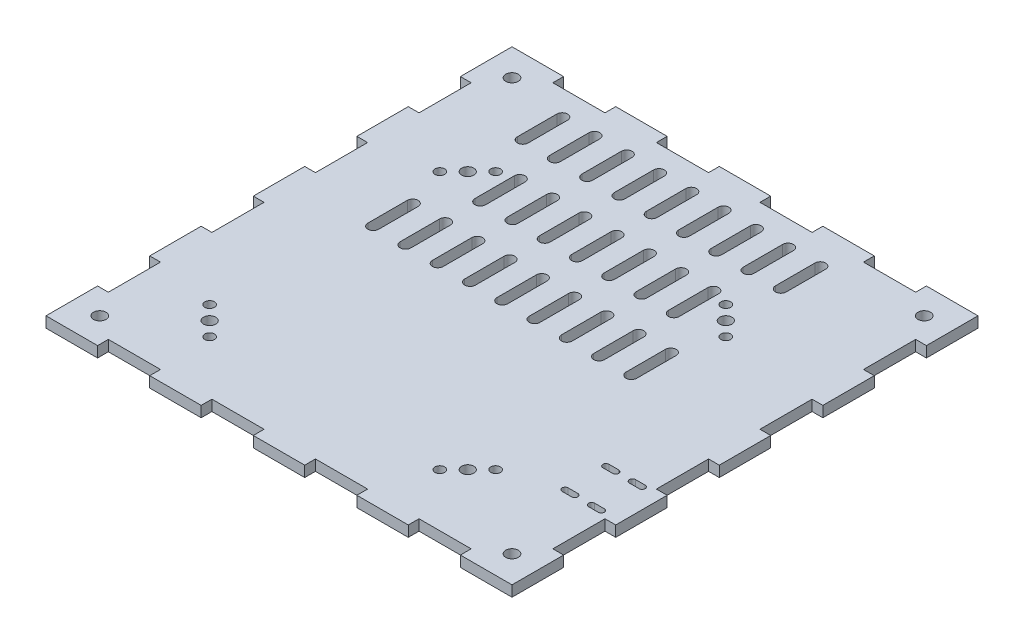
SolidWorks part; units mm, degrees
material "Acrylic (Medium-high impact)"
ref_plane "Front Plane" through (0, 0, 0) normal (0, 0, 1) x (1, 0, 0)
ref_plane "Top Plane" through (0, 0, 0) normal (0, 1, 0) x (1, 0, 0)
ref_plane "Right Plane" through (0, 0, 0) normal (1, 0, 0) x (0, 0, -1)
sketch "Board refrence" plane through (0, 0, 0) normal (0, 1, 0) x (1, 0, 0)
  line L0 (42.5, -17.26) -> (47.5, -17.26)
  line L1 (-40, -40) -> (40, -40)
  line L2 (-40, -40) -> (-40, 40)
  line L3 (-40, 40) -> (40, 40)
  line L4 (40, -40) -> (40, 40)
  line L5 (-40, -40) -> (40, 40) construction
  line L6 (-40, 40) -> (40, -40) construction
  line L7 (-50.8, 46.35) -> (50.8, 46.35)
  line L8 (-50.8, 46.35) -> (-50.8, 40)
  line L9 (-50.8, 40) -> (50.8, 40)
  line L10 (50.8, 46.35) -> (50.8, 40)
  line L11 (42.5, -25.26) -> (47.5, -25.26)
  line L12 (45, -25.26) -> (45, -17.26) construction
  circle A0 centre (-36, 36) radius 1.6
  circle A1 centre (-36, -36) radius 1.6
  circle A2 centre (36, -36) radius 1.6
  circle A3 centre (36, 36) radius 1.6
  point P0 (0, 0)
  point P14 (0, 40)
  point P15 (0, 40)
  point P26 (45, -21.26)
  dimension "D4" = 3.2
  dimension "D1" = 80
  dimension "D2" = 80
  dimension "D3" = 4
  dimension "D5" = 6.35
  dimension "D6" = 101.6
  dimension "D7" = 18.74
  dimension "D8" = 8
  dimension "D9" = 5
  dimension "D10" = 5
sketch "Sketch2" plane through (0, 0, 0) normal (0, 1, 0) x (1, 0, 0)
  line L0 (-40, -40) -> (-40, 40) construction
  line L1 (-56.8, 69.15) -> (66.8, 69.15) construction
  line L2 (-56.8, 69.15) -> (-56.8, -54.45) construction
  line L3 (-56.8, -54.45) -> (66.8, -54.45) construction
  line L4 (66.8, 69.15) -> (66.8, -54.45) construction
  line L6 (40, -40) -> (40, 40) construction
  line L7 (-50.8, 46.35) -> (50.8, 46.35) construction
  line L8 (-60, 72.35) -> (-60, -57.65)
  line L9 (-60, -57.65) -> (70, -57.65)
  line L10 (70, 72.35) -> (70, -57.65)
  line L11 (-60, 72.35) -> (70, 72.35)
  circle A0 centre (-36, 36) radius 1.7
  circle A1 centre (-36, -36) radius 1.7
  circle A2 centre (36, -36) radius 1.7
  circle A3 centre (36, 36) radius 1.7
  point P16 (0, 0)
  dimension "D1" = 3.4
  dimension "D2" = 20
  dimension "D3" = 26
  dimension "D4" = 30
  dimension "D6" = 130
  dimension "D7" = 130
  dimension "D5" = 3.2
extrude "Boss-Extrude1" add sketch "Sketch2" along normal blind 3
sketch "Sketch5" plane through (0, 3, 0) normal (0, 1, 0) x (1, 0, 0)
  line L0 (32.1109, 39.8891) -> (39.8891, 32.1109) construction
  line L1 (70, -57.65) -> (70, 72.35) construction
  circle A0 centre (39.8891, 32.1109) radius 1.35
  circle A1 centre (32.1109, 39.8891) radius 1.35
  circle A2 centre (32.1109, -39.8891) radius 1.35
  circle A3 centre (39.8891, -32.1109) radius 1.35
  circle A4 centre (-39.8891, -32.1109) radius 1.35
  circle A5 centre (-32.1109, -39.8891) radius 1.35
  circle A6 centre (-32.1109, 39.8891) radius 1.35
  circle A7 centre (-39.8891, 32.1109) radius 1.35
  point P4 (36, 36)
  point P23 (0, 0)
  dimension "D3" = 2.7
  dimension "D1" = 45
  dimension "D2" = 11
extrude "Cut-Extrude2" cut sketch "Sketch5" against normal up to next
sketch "Sketch4" plane through (0, 3, 0) normal (0, 1, 0) x (1, 0, 0)
  line L0 (70, 57.9056) -> (70, 43.4611)
  line L1 (70, -57.65) -> (70, 72.35) construction
  line L2 (70, 14.5722) -> (67, 14.5722)
  line L3 (67, 14.5722) -> (67, 29.0167)
  line L4 (67, 29.0167) -> (70, 29.0167)
  line L5 (70, 29.0167) -> (70, 14.5722)
  line L6 (70, -14.3167) -> (67, -14.3167)
  line L7 (67, -14.3167) -> (67, 0.1278)
  line L8 (67, 0.1278) -> (70, 0.1278)
  line L9 (70, 0.1278) -> (70, -14.3167)
  line L10 (70, 43.4611) -> (67, 43.4611)
  line L11 (67, 43.4611) -> (67, 57.9056)
  line L12 (67, 57.9056) -> (70, 57.9056)
  line L13 (70, -43.2056) -> (67, -43.2056)
  line L14 (67, -43.2056) -> (67, -28.7611)
  line L15 (67, -28.7611) -> (70, -28.7611)
  line L16 (70, -28.7611) -> (70, -43.2056)
  line L17 (70, 43.4611) -> (70, 14.5722) construction
  line L18 (67, -43.2056) -> (67, -57.65) construction
  line L19 (-60, -57.65) -> (70, -57.65) construction
  line L20 (67, -28.7611) -> (67, -14.3167) construction
  line L21 (70, 72.35) -> (-60, 72.35) construction
  line L42 (-60, 72.35) -> (70, -57.65) construction
  line L66 (-45.5556, -57.65) -> (-45.5556, -54.65)
  line L67 (-45.5556, -54.65) -> (-31.1111, -54.65)
  line L68 (-31.1111, -54.65) -> (-31.1111, -57.65)
  line L91 (67, 0.1278) -> (67, 14.5722) construction
  line L92 (67, 29.0167) -> (67, 43.4611) construction
  line L93 (67, 57.9056) -> (67, 72.35) construction
  line L94 (-31.1111, -57.65) -> (-45.5556, -57.65)
  line L95 (-16.6667, -57.65) -> (-16.6667, -54.65)
  line L96 (-16.6667, -54.65) -> (-2.2222, -54.65)
  line L97 (-2.2222, -54.65) -> (-2.2222, -57.65)
  line L103 (-2.2222, -57.65) -> (-16.6667, -57.65)
  line L108 (12.2222, -57.65) -> (12.2222, -54.65)
  line L113 (12.2222, -54.65) -> (26.6667, -54.65)
  line L118 (26.6667, -54.65) -> (26.6667, -57.65)
  line L119 (26.6667, -57.65) -> (12.2222, -57.65)
  line L120 (55.5556, -57.65) -> (41.1111, -57.65)
  line L121 (41.1111, -57.65) -> (41.1111, -54.65)
  line L125 (41.1111, -54.65) -> (55.5556, -54.65)
  line L126 (55.5556, -54.65) -> (55.5556, -57.65)
  line L127 (-60, 57.9056) -> (-57, 57.9056)
  line L128 (-57, 57.9056) -> (-57, 43.4611)
  line L129 (-57, 43.4611) -> (-60, 43.4611)
  line L130 (-60, 43.4611) -> (-60, 57.9056)
  line L131 (-60, 29.0167) -> (-57, 29.0167)
  line L132 (-57, 29.0167) -> (-57, 14.5722)
  line L133 (-57, 14.5722) -> (-60, 14.5722)
  line L134 (-60, 14.5722) -> (-60, 29.0167)
  line L135 (-60, 0.1278) -> (-57, 0.1278)
  line L136 (-57, 0.1278) -> (-57, -14.3167)
  line L137 (-57, -14.3167) -> (-60, -14.3167)
  line L138 (-60, -14.3167) -> (-60, 0.1278)
  line L139 (-60, -43.2056) -> (-60, -28.7611)
  line L140 (-60, -28.7611) -> (-57, -28.7611)
  line L141 (-57, -28.7611) -> (-57, -43.2056)
  line L142 (-57, -43.2056) -> (-60, -43.2056)
  line L143 (55.5556, 72.35) -> (55.5556, 69.35)
  line L144 (55.5556, 69.35) -> (41.1111, 69.35)
  line L145 (41.1111, 69.35) -> (41.1111, 72.35)
  line L146 (41.1111, 72.35) -> (55.5556, 72.35)
  line L147 (26.6667, 72.35) -> (26.6667, 69.35)
  line L148 (26.6667, 69.35) -> (12.2222, 69.35)
  line L149 (12.2222, 69.35) -> (12.2222, 72.35)
  line L150 (12.2222, 72.35) -> (26.6667, 72.35)
  line L151 (-2.2222, 72.35) -> (-2.2222, 69.35)
  line L152 (-2.2222, 69.35) -> (-16.6667, 69.35)
  line L153 (-16.6667, 69.35) -> (-16.6667, 72.35)
  line L154 (-16.6667, 72.35) -> (-2.2222, 72.35)
  line L155 (-45.5556, 72.35) -> (-31.1111, 72.35)
  line L156 (-31.1111, 72.35) -> (-31.1111, 69.35)
  line L157 (-31.1111, 69.35) -> (-45.5556, 69.35)
  line L158 (-45.5556, 69.35) -> (-45.5556, 72.35)
  point P27 (5, 7.35)
  point P81 (5, 7.35)
  dimension "D2" = 4
extrude "Cut tabs" cut sketch "Sketch4" against normal through all
sketch "Pad reference" plane through (0, 3, 0) normal (0, 1, 0) x (1, 0, 0)
  line L2 (-60, -57.65) -> (-45.5556, -57.65) construction
  line L3 (55, 57.35) -> (-45, 57.35) construction
  line L4 (55, 57.35) -> (55, -42.65) construction
  line L5 (55, -42.65) -> (-45, -42.65) construction
  line L7 (-45, 57.35) -> (-45, -42.65) construction
  line L151 (70, -57.65) -> (70, -43.2056) construction
  line L152 (70, 72.35) -> (55.5556, 72.35) construction
  circle A0 centre (-45, 57.35) radius 4
  circle A1 centre (55, 57.35) radius 4
  circle A2 centre (55, -42.65) radius 4
  circle A3 centre (-45, -42.65) radius 4
  dimension "D1" = 8
  dimension "D3" = 15
  dimension "D4" = 15
  dimension "D2" = 15
sketch "Sketch6" plane through (0, 3, 0) normal (0, 1, 0) x (1, 0, 0)
  line L0 (64.5, -27.2389) -> (61.8, -27.2389) construction
  line L1 (64.5, -28.0889) -> (61.8, -28.0889)
  line L2 (64.5, -26.3889) -> (61.8, -26.3889)
  line L3 (57.1, -27.2389) -> (54.4, -27.2389) construction
  line L4 (57.1, -28.0889) -> (54.4, -28.0889)
  line L5 (57.1, -26.3889) -> (54.4, -26.3889)
  line L6 (72.5, -21.5389) -> (-49927.5, -21.5389) construction
  line L7 (70, -28.7611) -> (70, -14.3167) construction
  line L8 (57.1, -15.8389) -> (54.4, -15.8389) construction
  line L9 (57.1, -14.9889) -> (54.4, -14.9889)
  line L10 (57.1, -16.6889) -> (54.4, -16.6889)
  line L11 (64.5, -15.8389) -> (61.8, -15.8389) construction
  line L12 (64.5, -14.9889) -> (61.8, -14.9889)
  line L13 (64.5, -16.6889) -> (61.8, -16.6889)
  arc A0 (64.5, -28.0889) -> (64.5, -26.3889) centre (64.5, -27.2389) ccw
  arc A1 (61.8, -26.3889) -> (61.8, -28.0889) centre (61.8, -27.2389) ccw
  arc A2 (57.1, -28.0889) -> (57.1, -26.3889) centre (57.1, -27.2389) ccw
  arc A3 (54.4, -26.3889) -> (54.4, -28.0889) centre (54.4, -27.2389) ccw
  arc A4 (57.1, -14.9889) -> (57.1, -16.6889) centre (57.1, -15.8389) cw
  arc A5 (54.4, -16.6889) -> (54.4, -14.9889) centre (54.4, -15.8389) cw
  arc A6 (64.5, -14.9889) -> (64.5, -16.6889) centre (64.5, -15.8389) cw
  arc A7 (61.8, -16.6889) -> (61.8, -14.9889) centre (61.8, -15.8389) cw
  point P2 (63.15, -27.2389)
  point P7 (55.75, -27.2389)
  point P18 (70, -21.5389)
  point P21 (55.75, -15.8389)
  point P28 (63.15, -15.8389)
  dimension "D3" = 3
  dimension "D1" = 4.4
  dimension "D2" = 1.7
  dimension "D4" = 4.85
  dimension "D5" = 5.5
extrude "Power cord slots" cut sketch "Sketch6" against normal up to next
sketch "Sketch7" plane through (0, 3, 0) normal (0, 1, 0) x (1, 0, 0)
  line L0 (-36, 62.35) -> (-36, 51.35) construction
  line L1 (-34.5, 62.35) -> (-34.5, 51.35)
  line L2 (-37.5, 62.35) -> (-37.5, 51.35)
  line L3 (-45.5556, 69.35) -> (-31.1111, 69.35) construction
  line L4 (-37.5, 20.65) -> (-37.5, 9.65)
  line L5 (-28.5, 62.35) -> (-28.5, 51.35)
  line L6 (-25.5, 62.35) -> (-25.5, 51.35)
  line L7 (-27, 62.35) -> (-27, 51.35) construction
  line L8 (-19.5, 62.35) -> (-19.5, 51.35)
  line L9 (-16.5, 62.35) -> (-16.5, 51.35)
  line L10 (-18, 62.35) -> (-18, 51.35) construction
  line L11 (-10.5, 62.35) -> (-10.5, 51.35)
  line L12 (-7.5, 62.35) -> (-7.5, 51.35)
  line L13 (-9, 62.35) -> (-9, 51.35) construction
  line L14 (-1.5, 62.35) -> (-1.5, 51.35)
  line L15 (1.5, 62.35) -> (1.5, 51.35)
  line L16 (0, 62.35) -> (0, 51.35) construction
  line L17 (7.5, 62.35) -> (7.5, 51.35)
  line L18 (10.5, 62.35) -> (10.5, 51.35)
  line L19 (9, 62.35) -> (9, 51.35) construction
  line L20 (16.5, 62.35) -> (16.5, 51.35)
  line L21 (19.5, 62.35) -> (19.5, 51.35)
  line L22 (18, 62.35) -> (18, 51.35) construction
  line L23 (25.5, 62.35) -> (25.5, 51.35)
  line L24 (28.5, 62.35) -> (28.5, 51.35)
  line L25 (27, 62.35) -> (27, 51.35) construction
  line L26 (34.5, 62.35) -> (34.5, 51.35)
  line L27 (37.5, 62.35) -> (37.5, 51.35)
  line L28 (36, 62.35) -> (36, 51.35) construction
  line L32 (-36, 36) -> (-36, 51.35) construction
  line L33 (-36, 36) -> (-36, 20.65) construction
  line L34 (-34.5, 20.65) -> (-34.5, 9.65)
  line L37 (-28.5, 41.5) -> (-28.5, 30.5)
  line L38 (-25.5, 41.5) -> (-25.5, 30.5)
  line L39 (-27, 41.5) -> (-27, 30.5) construction
  line L40 (-19.5, 41.5) -> (-19.5, 30.5)
  line L41 (-16.5, 41.5) -> (-16.5, 30.5)
  line L42 (-18, 41.5) -> (-18, 30.5) construction
  line L43 (-10.5, 41.5) -> (-10.5, 30.5)
  line L44 (-7.5, 41.5) -> (-7.5, 30.5)
  line L45 (-9, 41.5) -> (-9, 30.5) construction
  line L46 (-1.5, 41.5) -> (-1.5, 30.5)
  line L47 (1.5, 41.5) -> (1.5, 30.5)
  line L48 (0, 41.5) -> (0, 30.5) construction
  line L49 (7.5, 41.5) -> (7.5, 30.5)
  line L50 (10.5, 41.5) -> (10.5, 30.5)
  line L51 (9, 41.5) -> (9, 30.5) construction
  line L52 (16.5, 41.5) -> (16.5, 30.5)
  line L53 (19.5, 41.5) -> (19.5, 30.5)
  line L54 (18, 41.5) -> (18, 30.5) construction
  line L55 (25.5, 41.5) -> (25.5, 30.5)
  line L56 (28.5, 41.5) -> (28.5, 30.5)
  line L57 (27, 41.5) -> (27, 30.5) construction
  line L63 (-36, 20.65) -> (-36, 9.65) construction
  line L64 (-28.5, 20.65) -> (-28.5, 9.65)
  line L65 (-25.5, 20.65) -> (-25.5, 9.65)
  line L66 (-27, 20.65) -> (-27, 9.65) construction
  line L67 (-19.5, 20.65) -> (-19.5, 9.65)
  line L68 (-16.5, 20.65) -> (-16.5, 9.65)
  line L69 (-18, 20.65) -> (-18, 9.65) construction
  line L70 (-10.5, 20.65) -> (-10.5, 9.65)
  line L71 (-7.5, 20.65) -> (-7.5, 9.65)
  line L72 (-9, 20.65) -> (-9, 9.65) construction
  line L73 (-1.5, 20.65) -> (-1.5, 9.65)
  line L74 (1.5, 20.65) -> (1.5, 9.65)
  line L75 (0, 20.65) -> (0, 9.65) construction
  line L76 (7.5, 20.65) -> (7.5, 9.65)
  line L77 (10.5, 20.65) -> (10.5, 9.65)
  line L78 (9, 20.65) -> (9, 9.65) construction
  line L79 (16.5, 20.65) -> (16.5, 9.65)
  line L80 (19.5, 20.65) -> (19.5, 9.65)
  line L81 (18, 20.65) -> (18, 9.65) construction
  line L82 (25.5, 20.65) -> (25.5, 9.65)
  line L83 (28.5, 20.65) -> (28.5, 9.65)
  line L84 (27, 20.65) -> (27, 9.65) construction
  line L85 (34.5, 20.65) -> (34.5, 9.65)
  line L86 (37.5, 20.65) -> (37.5, 9.65)
  line L87 (36, 20.65) -> (36, 9.65) construction
  line L88 (34.5, 41.5) -> (34.5, 30.5) [skipped]
  line L89 (37.5, 41.5) -> (37.5, 30.5) [skipped]
  line L90 (-37.5, 41.5) -> (-37.5, 30.5) [skipped]
  line L91 (-34.5, 41.5) -> (-34.5, 30.5) [skipped]
  line L93 (-37.5, 62.35) -> (-28.5, 62.35) construction
  arc A0 (-34.5, 62.35) -> (-37.5, 62.35) centre (-36, 62.35) ccw
  arc A1 (-37.5, 51.35) -> (-34.5, 51.35) centre (-36, 51.35) ccw
  arc A2 (-25.5, 62.35) -> (-28.5, 62.35) centre (-27, 62.35) ccw
  arc A3 (-28.5, 51.35) -> (-25.5, 51.35) centre (-27, 51.35) ccw
  arc A4 (-16.5, 62.35) -> (-19.5, 62.35) centre (-18, 62.35) ccw
  arc A5 (-19.5, 51.35) -> (-16.5, 51.35) centre (-18, 51.35) ccw
  arc A6 (-7.5, 62.35) -> (-10.5, 62.35) centre (-9, 62.35) ccw
  arc A7 (-10.5, 51.35) -> (-7.5, 51.35) centre (-9, 51.35) ccw
  arc A8 (1.5, 62.35) -> (-1.5, 62.35) centre (0, 62.35) ccw
  arc A9 (-1.5, 51.35) -> (1.5, 51.35) centre (0, 51.35) ccw
  arc A10 (10.5, 62.35) -> (7.5, 62.35) centre (9, 62.35) ccw
  arc A11 (7.5, 51.35) -> (10.5, 51.35) centre (9, 51.35) ccw
  arc A12 (19.5, 62.35) -> (16.5, 62.35) centre (18, 62.35) ccw
  arc A13 (16.5, 51.35) -> (19.5, 51.35) centre (18, 51.35) ccw
  arc A14 (28.5, 62.35) -> (25.5, 62.35) centre (27, 62.35) ccw
  arc A15 (25.5, 51.35) -> (28.5, 51.35) centre (27, 51.35) ccw
  arc A16 (37.5, 62.35) -> (34.5, 62.35) centre (36, 62.35) ccw
  arc A17 (34.5, 51.35) -> (37.5, 51.35) centre (36, 51.35) ccw
  arc A20 (-25.5, 41.5) -> (-28.5, 41.5) centre (-27, 41.5) ccw
  arc A21 (-28.5, 30.5) -> (-25.5, 30.5) centre (-27, 30.5) ccw
  arc A22 (-16.5, 41.5) -> (-19.5, 41.5) centre (-18, 41.5) ccw
  arc A23 (-19.5, 30.5) -> (-16.5, 30.5) centre (-18, 30.5) ccw
  arc A24 (-7.5, 41.5) -> (-10.5, 41.5) centre (-9, 41.5) ccw
  arc A25 (-10.5, 30.5) -> (-7.5, 30.5) centre (-9, 30.5) ccw
  arc A26 (1.5, 41.5) -> (-1.5, 41.5) centre (0, 41.5) ccw
  arc A27 (-1.5, 30.5) -> (1.5, 30.5) centre (0, 30.5) ccw
  arc A28 (10.5, 41.5) -> (7.5, 41.5) centre (9, 41.5) ccw
  arc A29 (7.5, 30.5) -> (10.5, 30.5) centre (9, 30.5) ccw
  arc A30 (19.5, 41.5) -> (16.5, 41.5) centre (18, 41.5) ccw
  arc A31 (16.5, 30.5) -> (19.5, 30.5) centre (18, 30.5) ccw
  arc A32 (28.5, 41.5) -> (25.5, 41.5) centre (27, 41.5) ccw
  arc A33 (25.5, 30.5) -> (28.5, 30.5) centre (27, 30.5) ccw
  arc A36 (-34.5, 20.65) -> (-37.5, 20.65) centre (-36, 20.65) ccw
  arc A37 (-37.5, 9.65) -> (-34.5, 9.65) centre (-36, 9.65) ccw
  arc A38 (-25.5, 20.65) -> (-28.5, 20.65) centre (-27, 20.65) ccw
  arc A39 (-28.5, 9.65) -> (-25.5, 9.65) centre (-27, 9.65) ccw
  arc A40 (-16.5, 20.65) -> (-19.5, 20.65) centre (-18, 20.65) ccw
  arc A41 (-19.5, 9.65) -> (-16.5, 9.65) centre (-18, 9.65) ccw
  arc A42 (-7.5, 20.65) -> (-10.5, 20.65) centre (-9, 20.65) ccw
  arc A43 (-10.5, 9.65) -> (-7.5, 9.65) centre (-9, 9.65) ccw
  arc A44 (1.5, 20.65) -> (-1.5, 20.65) centre (0, 20.65) ccw
  arc A45 (-1.5, 9.65) -> (1.5, 9.65) centre (0, 9.65) ccw
  arc A46 (10.5, 20.65) -> (7.5, 20.65) centre (9, 20.65) ccw
  arc A47 (7.5, 9.65) -> (10.5, 9.65) centre (9, 9.65) ccw
  arc A48 (19.5, 20.65) -> (16.5, 20.65) centre (18, 20.65) ccw
  arc A49 (16.5, 9.65) -> (19.5, 9.65) centre (18, 9.65) ccw
  arc A50 (28.5, 20.65) -> (25.5, 20.65) centre (27, 20.65) ccw
  arc A51 (25.5, 9.65) -> (28.5, 9.65) centre (27, 9.65) ccw
  arc A52 (37.5, 20.65) -> (34.5, 20.65) centre (36, 20.65) ccw
  arc A53 (34.5, 9.65) -> (37.5, 9.65) centre (36, 9.65) ccw
  arc A54 (37.5, 41.5) -> (34.5, 41.5) centre (36, 41.5) ccw [skipped]
  arc A55 (34.5, 30.5) -> (37.5, 30.5) centre (36, 30.5) ccw [skipped]
  arc A56 (-34.5, 41.5) -> (-37.5, 41.5) centre (-36, 41.5) ccw [skipped]
  arc A57 (-37.5, 30.5) -> (-34.5, 30.5) centre (-36, 30.5) ccw [skipped]
  point P2 (-36, 56.85)
  point P12 (-37.5, 56.85)
  point P16 (-27, 56.85)
  point P23 (-18, 56.85)
  point P30 (-9, 56.85)
  point P37 (0, 56.85)
  point P44 (9, 56.85)
  point P51 (18, 56.85)
  point P58 (27, 56.85)
  point P65 (36, 56.85)
  point P86 (-27, 36)
  point P93 (-18, 36)
  point P100 (-9, 36)
  point P107 (0, 36)
  point P114 (9, 36)
  point P121 (18, 36)
  point P128 (27, 36)
  point P140 (-36, 15.15)
  point P149 (-27, 15.15)
  point P156 (-18, 15.15)
  point P163 (-9, 15.15)
  point P170 (0, 15.15)
  point P177 (9, 15.15)
  point P184 (18, 15.15)
  point P191 (27, 15.15)
  point P198 (36, 15.15)
  dimension "D1" = 7
  dimension "D2" = 11
  dimension "D4" = 3
  dimension "D7" = 9
  dimension "D5" = 9
  dimension "D6" = 3
extrude "Cooling slots" cut sketch "Sketch7" against normal up to next (3 mm away)
sketch "Sketch8" plane through (0, 3, 0) normal (0, 1, 0) x (1, 0, 0)
  line L1 (-60, 72.35) -> (70, 72.35) construction
  line L2 (-60, 72.35) -> (-60, -57.65) construction
  line L3 (-60, -57.65) -> (70, -57.65) construction
  line L4 (70, 72.35) -> (70, -57.65) construction
  line L72 (-52.5, 64.85) -> (-52.5, -50.15) construction
  line L73 (-52.5, -50.15) -> (62.5, -50.15) construction
  line L74 (62.5, 64.85) -> (62.5, -50.15) construction
  line L75 (-52.5, 64.85) -> (62.5, 64.85) construction
  circle A0 centre (-52.5, 64.85) radius 1.75
  circle A1 centre (62.5, 64.85) radius 1.75
  circle A2 centre (62.5, -50.15) radius 1.75
  circle A3 centre (-52.5, -50.15) radius 1.75
  dimension "D1" = 3.5
  dimension "D2" = 7.5
extrude "Cornerpiece holes" cut sketch "Sketch8" against normal up to next
other "Tolerance" flip direction yes face at (41.1111, 1.5, -70.85) face at (12.2222, 1.5, -70.85) face at (-16.6667, 1.5, -70.85) face at (-45.5556, 1.5, -70.85) face at (26.6667, 1.5, -70.85) face at (55.5556, 1.5, -70.85) face at (-2.2222, 1.5, -70.85) face at (-31.1111, 1.5, -70.85) face at (-58.5, 1.5, -43.4611) face at (-58.5, 1.5, -57.9056) face at (-58.5, 1.5, -14.5722) face at (-58.5, 1.5, -29.0167) face at (-58.5, 1.5, -0.1278) face at (-58.5, 1.5, 14.3167) face at (-58.5, 1.5, 43.2056) face at (-58.5, 1.5, 28.7611) face at (-31.1111, 1.5, 56.15) face at (-45.5556, 1.5, 56.15) face at (-16.6667, 1.5, 56.15) face at (-2.2222, 1.5, 56.15) face at (12.2222, 1.5, 56.15) face at (26.6667, 1.5, 56.15) face at (55.5556, 1.5, 56.15) face at (41.1111, 1.5, 56.15) face at (68.5, 1.5, 28.7611) face at (68.5, 1.5, 43.2056) face at (68.5, 1.5, 14.3167) face at (68.5, 1.5, -0.1278) face at (68.5, 1.5, -14.5722) face at (68.5, 1.5, -29.0167) face at (68.5, 1.5, -57.9056) face at (68.5, 1.5, -43.4611) offset 0.05 parameters "D1"=0.05
equation "\"D5@Board refrence\" =  ( 1 / 4 )  * 1in"
equation "\"D6@Board refrence\" = 4in"
equation "\"slot_depth\"= 3mm"
equation "\"slot_width_tolerance\"= 0.05mm"
equation "\"D4@Sketch4\"=\"slot_depth\""
equation "\"D2@Sketch8\"=4.50+\"slot_depth\""
